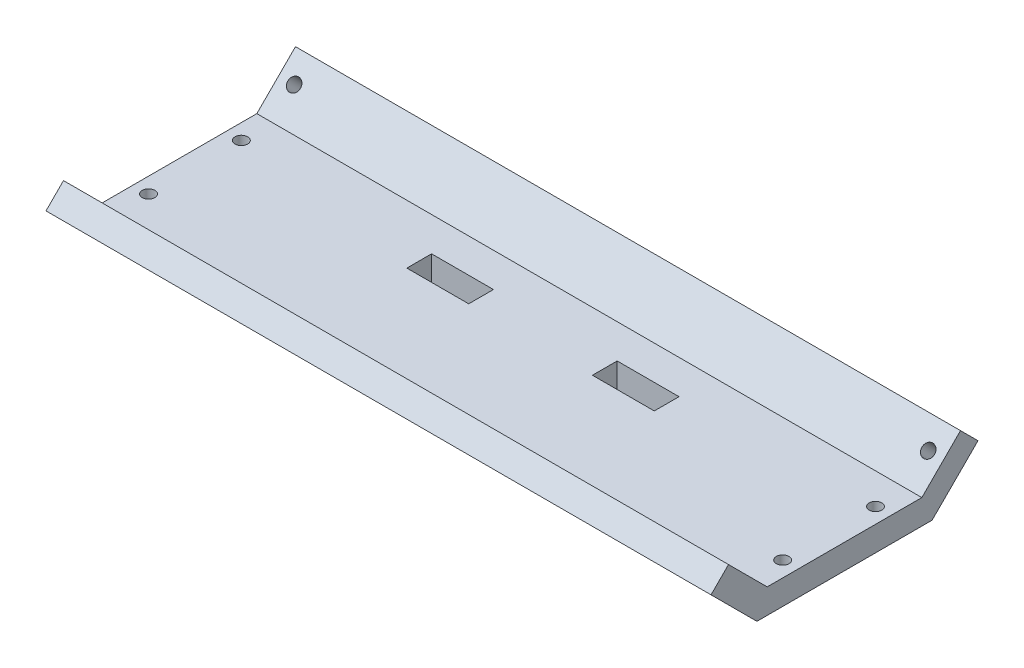
SolidWorks part; units mm, degrees
material "ABS"
ref_plane "Front Plane" through (0, 0, 0) normal (0, 0, 1) x (1, 0, 0)
ref_plane "Top Plane" through (0, 0, 0) normal (0, 1, 0) x (1, 0, 0)
ref_plane "Right Plane" through (0, 0, 0) normal (1, 0, 0) x (0, 0, -1)
sketch "Sketch2" plane through (0, 0, 0) normal (1, 0, 0) x (0, 0, -1)
  line L0 (-25, 0) -> (25, 0)
  line L1 (25, 0) -> (37.5, 12.5)
  line L2 (-25, 0) -> (-37.5, 12.5)
  line L8 (28.3137, -8) -> (43.1569, 6.8431)
  line L9 (-28.3137, -8) -> (28.3137, -8)
  line L10 (-28.3137, -8) -> (-43.1569, 6.8431)
  line L11 (-37.5, 12.5) -> (-43.1569, 6.8431)
  line L12 (37.5, 12.5) -> (43.1569, 6.8431)
  line L13 (-37.5, 12.5) -> (-50, 25) construction
  line L14 (37.5, 12.5) -> (50, 25) construction
  point P4 (0, 0)
  dimension "D2" = 135
  dimension "D3" = 135
  dimension "D1" = 100
  dimension "D4" = 25
  dimension "D5" = 8
extrude "Main" add sketch "Sketch2" along normal mid plane 215
hole_wizard "Ø4.0mm Dowel Hole2" positions "3DSketch2" profile "Sketch4" hole size "Ø4.0" standard "ANSI Metric" end condition through all
sketch3d "3DSketch2"
  line L2 (107.5, 0, -25) -> (-107.5, 0, -25) construction
  line L3 (-102.5, 0, -25) -> (-102.5, 0, -15) construction
  line L4 (-102.5, 0, -15) -> (-102.5, 0, 15) construction
  line L5 (-102.5, 0, 15) -> (-102.5, 0, 25) construction
  line L6 (107.5, 0, 25) -> (-107.5, 0, 25) construction
  line L11 (102.5, 0, -25) -> (102.5, 0, -15) construction
  line L12 (102.5, 0, -15) -> (102.5, 0, 15) construction
  line L13 (102.5, 0, 15) -> (102.5, 0, 25) construction
  line L27 (102.5, 0, -25) -> (102.5, 7.0711, -32.0711) construction
  line L29 (102.5, 0, 25) -> (102.5, 7.0711, 32.0711) construction
  line L31 (-102.5, 7.0711, 32.0711) -> (-102.5, 0, 25) construction
  line L35 (-102.5, 7.0711, -32.0711) -> (-107.5, 7.0711, -32.0711) construction
  line L36 (-107.5, 12.5, -37.5) -> (-107.5, 0, -25) construction
  line L38 (-102.5, 7.0711, 32.0711) -> (-107.5, 7.0711, 32.0711) construction
  line L39 (-107.5, 0, 25) -> (-107.5, 12.5, 37.5) construction
  line L41 (102.5, 7.0711, -32.0711) -> (107.5, 7.0711, -32.0711) construction
  line L42 (107.5, 12.5, -37.5) -> (107.5, 0, -25) construction
  line L44 (102.5, 7.0711, 32.0711) -> (107.5, 7.0711, 32.0711) construction
  line L45 (107.5, 0, 25) -> (107.5, 12.5, 37.5) construction
  line L47 (102.5, 0, 25) -> (107.5, 0, 25) construction
  line L49 (-102.5, 0, 25) -> (-107.5, 0, 25) construction
  line L51 (-102.5, 7.0711, -32.0711) -> (-102.5, 0, -25) construction
  point P0 (-102.5, 7.0711, -32.0711)
  point P2 (-102.5, 0, -15)
  point P4 (-102.5, 0, 15)
  point P6 (-102.5, 7.0711, 32.0711)
  point P8 (102.5, 7.0711, 32.0711)
  point P10 (102.5, 0, 15)
  point P12 (102.5, 0, -15)
  point P14 (102.5, 7.0711, -32.0711)
  dimension "D1" = 5
  dimension "D2" = 10
  dimension "D3" = 10
sketch "Sketch4" plane through (-102.5, 7.0711, -32.0711) normal (1, 0, 0) x (0, -0.7071, 0.7071)
  line L0 (0, 0) -> (0, 18.4957)
  line L1 (0, 18.4957) -> (2.05, 18.4957)
  line L2 (2.05, 18.4957) -> (2.05, 0)
  line L5 (2.05, 0) -> (0, 0)
  line L11 (0, -6.35) -> (0, 107.95) construction
  dimension "Thru Hole Dia." = 4.1
  dimension "Thru Hole Depth" = 18.4957
sketch "Sketch5" plane through (0, 0, 0) normal (0, 1, 0) x (1, 0, 0)
  line L1 (-33.5, 21) -> (33.5, 21) construction
  line L2 (-33.5, 21) -> (-33.5, -21) construction
  line L3 (-33.5, -21) -> (33.5, -21) construction
  line L4 (33.5, 21) -> (33.5, -21) construction
  line L5 (-33.5, 21) -> (33.5, -21) construction
  line L6 (-33.5, -21) -> (33.5, 21) construction
  circle A0 centre (-33.5, 21) radius 3.5
  circle A1 centre (33.5, 21) radius 3.5
  circle A2 centre (-33.5, -21) radius 3.5
  circle A3 centre (33.5, -21) radius 3.5
  circle A4 centre (-33.5, 21) radius 1.55
  circle A5 centre (33.5, 21) radius 1.55
  circle A6 centre (33.5, -21) radius 1.55
  circle A7 centre (-33.5, -21) radius 1.55
  point P0 (0, 0)
  dimension "D1" = 7
  dimension "D2" = 3.1
  dimension "D3" = 42
  dimension "D4" = 67
extrude "Boss-Extrude1" [suppressed] add sketch "Sketch5" along normal blind 12
sketch "Sketch6" plane through (0, 0, 0) normal (0, 1, 0) x (1, 0, 0)
  line L0 (0, 0) -> (0, 10) construction
  line L1 (20, 14) -> (40, 14)
  line L2 (20, 14) -> (20, 6)
  line L3 (20, 6) -> (40, 6)
  line L4 (40, 14) -> (40, 6)
  line L5 (20, 14) -> (40, 6) construction
  line L6 (20, 6) -> (40, 14) construction
  line L7 (30, 10) -> (0, 10) construction
  line L8 (-40, 14) -> (-20, 14)
  line L9 (-40, 14) -> (-40, 6)
  line L10 (-40, 6) -> (-20, 6)
  line L11 (-20, 14) -> (-20, 6)
  line L12 (-40, 14) -> (-20, 6) construction
  line L13 (-40, 6) -> (-20, 14) construction
  line L14 (0, 10) -> (-30, 10) construction
  point P0 (30, 10)
  point P5 (-30, 10)
  dimension "D1" = 80
  dimension "D2" = 8
  dimension "D3" = 40
  dimension "D4" = 10
extrude "Shelf cut" cut sketch "Sketch6" against normal through all
equation "\"length\" = 215mm"
equation "\"D1@Main\" = \"length\""
equation "\"width\" = 220mm"
equation "\"height\" = 100mm"
equation "\"skin_th\" = 8mm"
equation "\"D5@Sketch2\"=\"skin_th\""
equation "\"D1@Sketch2\"=\"height\""
equation "\"shelf_height\" = 10mm"
equation "\"D4@Sketch6\"=\"shelf_height\""
equation "\"D2@Sketch6\"=\"skin_th\""
